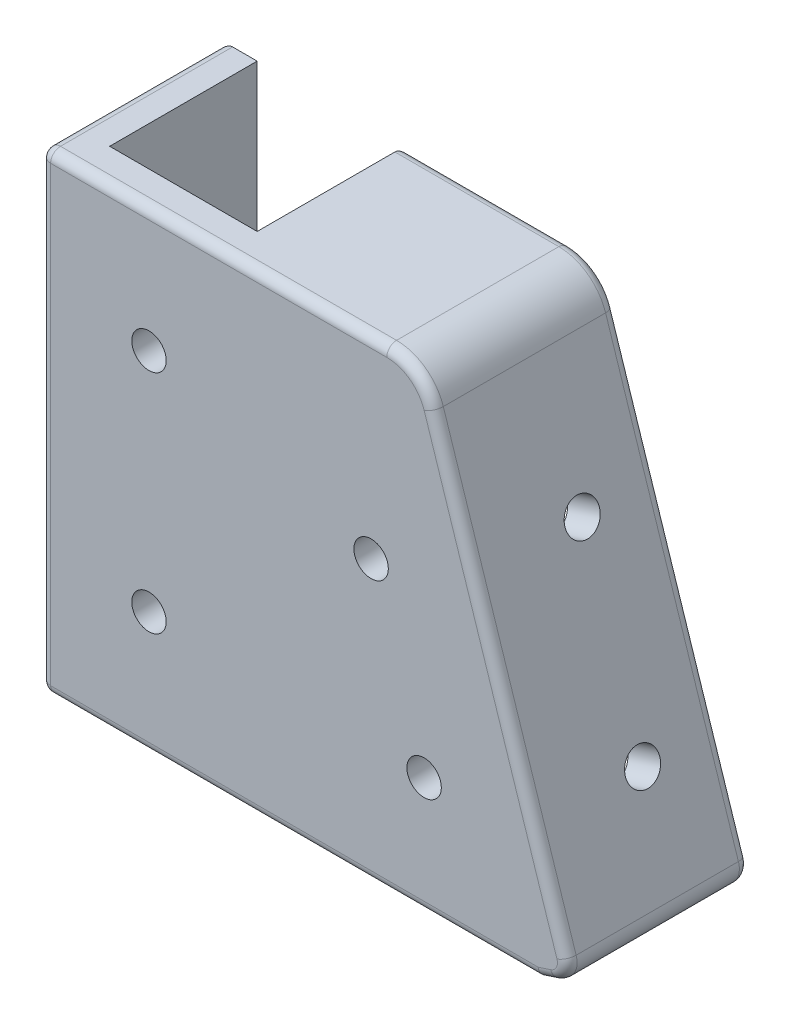
SolidWorks part; units mm, degrees
ref_plane "Front Plane" through (0, 0, 0) normal (0, 0, 1) x (1, 0, 0)
ref_plane "Top Plane" through (0, 0, 0) normal (0, 1, 0) x (1, 0, 0)
ref_plane "Right Plane" through (0, 0, 0) normal (1, 0, 0) x (0, 0, -1)
sketch "Sketch1" plane through (0, 0, 0) normal (0, 0, 1) x (1, 0, 0)
  line L0 (18.1306, 13.619) -> (33.7267, -34.381)
  line L2 (-20.676, 13.619) -> (-20.676, -34.381)
  line L3 (-20.676, -34.381) -> (1.324, -34.381)
  line L4 (1.324, 38.1507) -> (1.324, -34.381) construction
  line L5 (33.7267, -34.381) -> (1.324, -34.381)
  line L6 (10.5945, -34.381) -> (1.324, -5.8493) construction
  line L7 (1.324, -5.8493) -> (41.3819, 7.1663) construction
  line L8 (18.1306, 13.619) -> (-20.676, 13.619)
  dimension "D1" = 22
  dimension "D2" = 18
  dimension "D3" = 22
  dimension "D4" = 30
  dimension "D5" = 48
extrude "Boss-Extrude1" add sketch "Sketch1" along normal blind 18.5
sketch "Sketch2" plane through (0, 0, 0) normal (0, 0, 1) x (1, 0, 0)
  line L1 (-20.676, -34.381) -> (33.7267, -34.381) construction
  line L2 (-17.176, 13.619) -> (-2.176, 13.619)
  line L3 (-17.176, 13.619) -> (-17.176, -34.381)
  line L4 (-17.176, -34.381) -> (-2.176, -34.381)
  line L5 (-2.176, 13.619) -> (-2.176, -34.381)
  line L6 (-20.676, 13.619) -> (-20.676, -34.381) construction
  line L7 (30.0466, -34.381) -> (16.1798, 8.2965)
  line L8 (16.1798, 8.2965) -> (1.914, 3.6613)
  line L9 (1.914, 3.6613) -> (14.2746, -34.381)
  line L10 (14.2746, -34.381) -> (30.0466, -34.381)
  line L11 (33.7267, -34.381) -> (18.1306, 13.619) construction
  line L12 (18.1306, 13.619) -> (-20.676, 13.619) construction
  dimension "D1" = 15
  dimension "D2" = 3.5
  dimension "D3" = 3.5
  dimension "D4" = 15
  dimension "D5" = 40
extrude "Cut-Extrude1" cut sketch "Sketch2" along normal offset from surface (15 mm away) 15 up to face at (2.6263, -10.381, 0)
sketch "Sketch3" plane through (20.4018, 6.6289, 0) normal (0.9511, 0.309, 0) x (0, 0, -1)
  line L0 (-7.5, 30.2721) -> (-7.5, -43.1204) construction
  line L1 (-15, 2.8906) -> (0, 2.8906) construction
  line L2 (-18.5, -43.1204) -> (0, -43.1204) construction
  line L3 (-15, -41.9831) -> (0, -41.9831) construction
  circle A0 centre (-7.5, -29.4831) radius 1.75
  circle A2 centre (-7.5, -9.6094) radius 1.75
  dimension "D1" = 3.5
  dimension "D2" = 12.5
  dimension "D3" = 12.5
extrude "Cut-Extrude2" cut sketch "Sketch3" against normal blind 3.5
sketch "Sketch4" plane through (0, 0, 18.5) normal (0, 0, -1) x (-1, 0, 0)
  line L0 (9.676, 13.619) -> (9.676, -34.381) construction
  line L1 (-18.1306, 13.619) -> (20.676, 13.619) construction
  line L2 (20.676, -34.381) -> (17.176, -34.381) construction
  line L3 (-9.0469, 5.9789) -> (-22.1606, -34.381) construction
  line L4 (-1.914, 3.6613) -> (-16.1798, 8.2965) construction
  line L5 (-16.1798, 8.2965) -> (-1.914, 3.6613) construction
  line L6 (20.676, 13.619) -> (20.676, -34.381) construction
  line L7 (-14.2746, -34.381) -> (-30.0466, -34.381) construction
  circle A0 centre (-18.2979, -22.4928) radius 1.75
  circle A2 centre (-12.9096, -5.9093) radius 1.75
  circle A4 centre (9.676, 1.119) radius 1.75
  circle A6 centre (9.676, -21.881) radius 1.75
  circle A7 centre (9.676, 12.619) radius 1.75 [skipped]
  circle A8 centre (9.676, -10.381) radius 1.75 [skipped]
  dimension "D1" = 12.5
  dimension "D2" = 12.5
  dimension "D4" = 3.5
  dimension "D5" = 4
  dimension "D6" = 12.5
  dimension "D7" = 11
  dimension "D8" = 12.5
extrude "Cut-Extrude3" cut sketch "Sketch4" along normal blind 4
sketch "Sketch5" plane through (-20.676, 0, 0) normal (-1, 0, 0) x (0, 0, 1)
  line L0 (7.5, 39.9696) -> (7.5, -34.381) construction
  line L2 (18.5, -34.381) -> (0, -34.381) construction
  line L3 (18.5, 13.619) -> (0, 13.619) construction
  line L4 (0, 13.619) -> (0, -34.381) construction
  circle A0 centre (7.5, -21.881) radius 1.75
  circle A2 centre (7.5, 1.119) radius 1.75
  circle A4 centre (7.5, 12.619) radius 1.75 [skipped]
  circle A5 centre (7.5, -10.381) radius 1.75 [skipped]
  dimension "D2" = 3.5
  dimension "D3" = 12.5
  dimension "D5" = 12.5
  dimension "D1" = 7.5
  dimension "D4" = 4
extrude "Cut-Extrude4" cut sketch "Sketch5" against normal blind 4
sketch "Sketch6" plane through (0, 0, 18.5) normal (0, 0, 1) x (1, 0, 0)
  line L0 (30.0466, -34.381) -> (33.3753, -33.2994)
  line L1 (33.7267, -34.381) -> (18.1306, 13.619) construction
  line L2 (33.3753, -33.2994) -> (33.7267, -34.381)
  line L3 (33.7267, -34.381) -> (30.0466, -34.381)
  line L4 (-20.676, -34.381) -> (33.7267, -34.381) construction
extrude "Cut-Extrude5" cut sketch "Sketch6" against normal blind 19
fillet "Fillet1" radius 2 1 edges at (33.3753, -33.2994, 9.25)
fillet "Fillet2" radius 5 1 edges at (18.1306, 13.619, 9.25)
fillet "Fillet3" radius 1 17 edges at (30.7599, -34.1492, 0) (32.6371, -32.9233, 0) (6.1609, 13.619, 0) (17.4368, 12.6641, 0) (30.7599, -34.1492, 18.5) (32.6371, -32.9233, 18.5) (-3.0891, 13.619, 18.5) (17.4368, 12.6641, 18.5) (-20.676, 13.619, 9.25) (-20.676, -34.381, 9.25) (-20.676, -10.381, 0) (6.0493, -34.381, 0) (-2.176, -10.381, 0) (26.0052, -10.6166, 0) (-20.676, -10.381, 18.5) (4.6853, -34.381, 18.5) (26.0052, -10.6166, 18.5)
